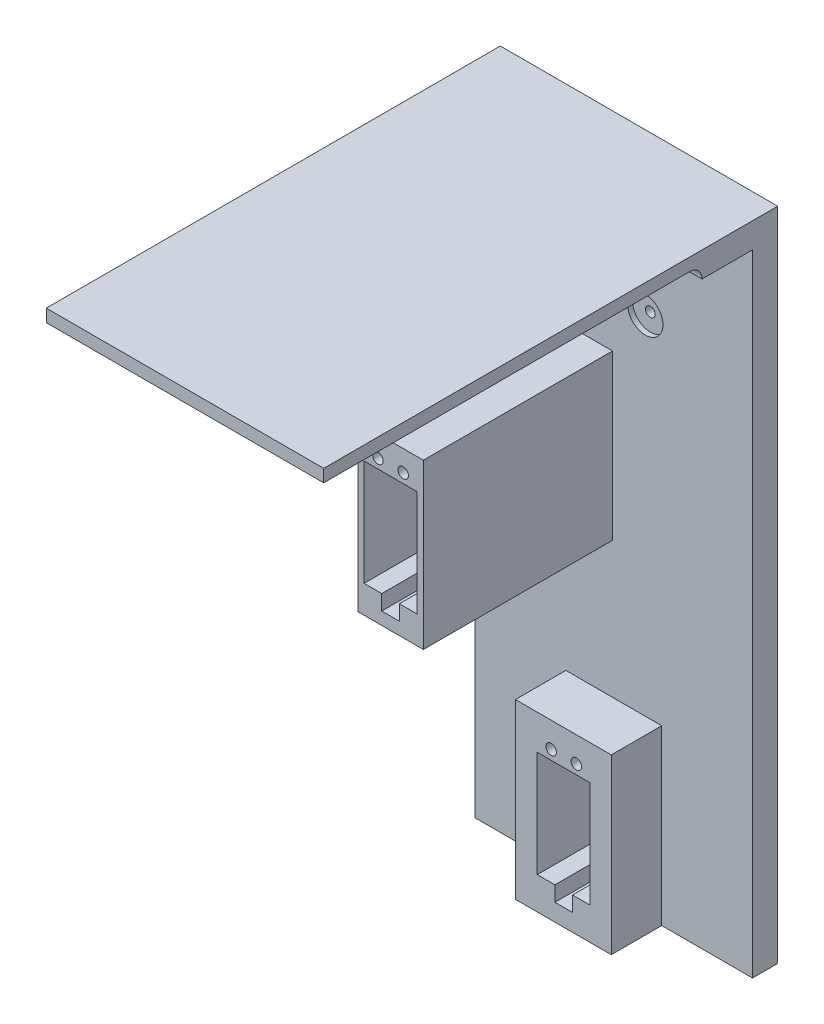
SolidWorks part; units mm, degrees
ref_plane "Front Plane" through (0, 0, 0) normal (0, 0, 1) x (1, 0, 0)
ref_plane "Top Plane" through (0, 0, 0) normal (0, 1, 0) x (1, 0, 0)
ref_plane "Right Plane" through (0, 0, 0) normal (1, 0, 0) x (0, 0, -1)
sketch "Sketch1" plane through (0, 0, 0) normal (0, 0, 1) x (1, 0, 0)
  line L1 (-75, 100) -> (75, 100)
  line L2 (-75, 100) -> (-75, -100)
  line L3 (-75, -100) -> (75, -100)
  line L4 (75, 100) -> (75, -100)
  line L5 (-75, 100) -> (75, -100) construction
  line L6 (-75, -100) -> (75, 100) construction
  point P0 (0, 0)
  dimension "D1" = 200
  dimension "D2" = 150
extrude "Boss-Extrude1" add sketch "Sketch1" along normal blind 30
sketch "Sketch2" plane through (0, 0, 30) normal (0, 0, 1) x (1, 0, 0)
  line L0 (75, -100) -> (75, 100) construction
  line L1 (-75, 100) -> (75, 100)
  line L2 (-75, 100) -> (-75, 95)
  line L3 (-75, 95) -> (75, 95)
  line L4 (75, 100) -> (75, 95)
  dimension "D1" = 5
extrude "Boss-Extrude2" add sketch "Sketch2" along normal blind 150
sketch "Sketch3" plane through (0, 0, 30) normal (0, 0, 1) x (1, 0, 0)
  line L0 (0, -100) -> (0, 0)
  line L1 (-75, -100) -> (75, -100) construction
  line L4 (0, 46.5) -> (0, 71.5)
  line L9 (-10.3251, 73.9819) -> (12.4051, 43.2014) construction
  line L10 (-12.4051, 43.2014) -> (10.3251, 73.9819) construction
  line L11 (-39.5, 13) -> (-39.5, 7)
  line L25 (-43, 13) -> (-36, 7) construction
  line L26 (-43, 7) -> (-36, 13) construction
  line L27 (-15.8, 46.5) -> (-12.5, 46.5)
  line L28 (-12.5, 46.5) -> (12.5, 46.5)
  line L29 (-12.5, 59) -> (12.5, 59)
  line L30 (12.5, 46.5) -> (-12.5, 46.5)
  line L31 (12.5, 46.5) -> (12.5, 71.5)
  line L32 (12.5, 71.5) -> (-12.5, 71.5)
  line L33 (-12.5, 46.5) -> (-12.5, 71.5)
  circle A0 centre (12.5, 46.5) radius 1.65
  circle A1 centre (-12.5, 46.5) radius 1.65
  circle A2 centre (12.5, 71.5) radius 1.65
  circle A3 centre (-12.5, 71.5) radius 1.65
  circle A4 centre (-12.5, 71.5) radius 3.3
  circle A5 centre (12.5, 71.5) radius 3.3
  circle A6 centre (12.5, 46.5) radius 3.3
  circle A7 centre (-12.5, 46.5) radius 3.3
  point P5 (0, 60)
  point P22 (-39.5, 10)
  dimension "D13" = 3.3
  dimension "D14" = 6.6
  dimension "D7" = 6
  dimension "D8" = 7
  dimension "D11" = 25
  dimension "D12" = 25
extrude "Cut-Extrude3" cut sketch "Sketch3" against normal blind 80 contours L11 | L11 | A1 L27 L33 | A1 L28 L27 | A1 L33 L28 | L31 A0 L30 | L30 A0 L31 | A2 L32 L31 | A2 L31 L32 | L32 A3 L33 | L33 A3 L32 region at (-12.5, 45.7997, 30) region at (-11.7997, 47.2003, 30) region at (11.7997, 47.2003, 30) region at (12.7334, 46.2666, 30) region at (-13.2003, 47.2003, 30) region at (-11.7997, 70.7997, 30) region at (-12.7334, 71.7334, 30) region at (12.7334, 71.7334, 30) region at (11.7997, 70.7997, 30)
ref_plane "Plane1" through (0, 0, 30) normal (0, 0, 1) x (1, 0, 0)
sketch "Sketch6" plane through (0, 0, 30) normal (0, 0, 1) x (1, 0, 0)
  circle A0 centre (-12.5, 71.5) radius 5
  circle A1 centre (12.5, 71.5) radius 5
  circle A2 centre (-12.5, 46.5) radius 5
  circle A3 centre (12.5, 46.5) radius 5
  dimension "D1" = 10
  dimension "D2" = 10
  dimension "D3" = 10
  dimension "D4" = 10
extrude "Cut-Extrude5" cut sketch "Sketch6" against normal blind 22
sketch "Sketch7" plane through (0, 0, 8) normal (0, 0, 1) x (1, 0, 0)
  circle A0 centre (-12.5, 71.5) radius 1.925
  circle A1 centre (12.5, 71.5) radius 1.925
  circle A2 centre (-12.5, 46.5) radius 1.925
  circle A3 centre (12.5, 46.5) radius 1.925
  dimension "D1" = 3.85
  dimension "D2" = 3.85
  dimension "D3" = 3.85
  dimension "D4" = 3.85
extrude "Cut-Extrude6" cut sketch "Sketch7" against normal blind 5
sketch "Sketch9" plane through (0, 0, 30) normal (0, 0, 1) x (1, 0, 0)
  line L0 (-12.5, 46.5) -> (12.5, 46.5)
  line L1 (12.5, 46.5) -> (0, 46.5)
  line L2 (0, 46.5) -> (1.1812, -69.9316)
  line L3 (1.1812, -69.9316) -> (1.1812, -115.5276)
  line L4 (-13.5, 15.5) -> (0.3145, 15.5)
  line L5 (-2.604, -89.8179) -> (4.396, -89.8179)
  line L6 (11.396, -83.8179) -> (11.396, -41.8179)
  line L7 (-2.604, -83.8179) -> (-9.604, -83.8179)
  line L8 (4.396, -89.8179) -> (4.396, -83.8179)
  line L9 (4.396, -83.8179) -> (11.396, -83.8179)
  line L10 (-9.604, -41.8179) -> (-9.604, -83.8179)
  line L11 (-24, 15.5) -> (-3, 15.5)
  line L12 (-17, -26.5) -> (-24, -26.5)
  line L18 (-24, 15.5) -> (-24, -26.5)
  line L19 (-10, -32.5) -> (-10, -26.5)
  line L20 (-17, -32.5) -> (-10, -32.5)
  line L21 (-17, -26.5) -> (-17, -32.5)
  line L22 (-10, -26.5) -> (-3, -26.5)
  line L23 (-3, -26.5) -> (-3, 15.5)
  line L24 (-9.604, -41.8179) -> (11.396, -41.8179)
  line L25 (-2.604, -83.8179) -> (-2.604, -89.8179)
  circle A6 centre (-8.5, 19.25) radius 2.08
  circle A7 centre (-18.5, 19.25) radius 2.08
  circle A8 centre (5.896, -38.0679) radius 2.08
  circle A9 centre (-4.104, -38.0679) radius 2.08
  point P16 (-39.5, 65.9329)
  dimension "D6" = 42
  dimension "D1" = 13.8145
fillet "Fillet1" radius 5 1 edges at (0, 95, 30)
extrude "Cut-Extrude7" cut sketch "Sketch9" against normal blind 30 contours L22 L23 L11 L18 L12 L21 L20 L19 | A7 | A6 region at (-13.5, -6.5909, 30) region at (-8.5, 19.25, 30) region at (-18.5, 19.25, 30)
sketch "Sketch10" plane through (0, 0, 30) normal (0, 0, 1) x (1, 0, 0)
  line L8 (0.1568, -105.1715) -> (0.1568, -105.1715)
  line L9 (8.2068, -105.9215) -> (-7.8932, -105.9215) construction
ref_plane "Plane2" through (0, 0, 0) normal (0, 0, -1) x (-1, 0, 0)
sketch "Sketch12" plane through (0, 0, 0) normal (0, 0, -1) x (-1, 0, 0)
  line L0 (13.5, 15.5) -> (13.5, -37.4614)
  line L1 (24, 15.5) -> (3, 15.5) construction
  line L2 (13.5, -37.4614) -> (26.5, -37.4614)
  line L3 (26.5, -37.4614) -> (26.5, 27.5386)
  line L4 (3, 15.5) -> (3, -26.5)
  line L5 (26.5, -37.4614) -> (0.5, -37.4614)
  line L6 (26.5, -37.4614) -> (26.5, 27.5386)
  line L7 (26.5, 27.5386) -> (0.5, 27.5386)
  line L8 (0.5, -37.4614) -> (0.5, 27.5386)
  line L9 (3, -26.5) -> (10, -26.5)
  line L10 (10, -26.5) -> (10, -32.5)
  line L11 (10, -32.5) -> (17, -32.5)
  line L12 (17, -32.5) -> (17, -26.5)
  line L13 (17, -26.5) -> (24, -26.5)
  line L14 (24, -26.5) -> (24, 15.5)
  line L15 (24, 15.5) -> (3, 15.5)
  circle A0 centre (8.5, 19.25) radius 2.08
  circle A1 centre (18.5, 19.25) radius 2.08
  dimension "D1" = 13
  dimension "D2" = 65
  dimension "D3" = 26
  dimension "D4" = 65
extrude "Boss-Extrude5" add sketch "Sketch12" against normal blind 85 contours L15 L14 L13 L12 L11 L2 L3 L7 L8 L5 L10 L9 L4 A1 A0 region at (-7, -36.7613, 0)
sketch "Sketch13" plane through (0, 0, 0) normal (0, 0, -1) x (-1, 0, 0)
  line L0 (-75, -100) -> (-75, -160)
  line L1 (-75, -160) -> (75, -160)
  line L2 (75, -160) -> (75, -100)
  line L3 (75, -100) -> (-75, -100) construction
  line L4 (75, -100) -> (-75, -100)
  dimension "D1" = 60
extrude "Boss-Extrude6" add sketch "Sketch13" against normal blind 30
sketch "Sketch15" plane through (0, 0, 30) normal (0, 0, 1) x (1, 0, 0)
  line L0 (-10.3432, -105.1715) -> (10.6568, -105.1715)
  line L1 (10.6568, -105.1715) -> (10.6568, -147.1715)
  line L2 (10.6568, -147.1715) -> (3.6568, -147.1715)
  line L3 (3.6568, -147.1715) -> (3.6568, -153.1715)
  line L4 (3.6568, -153.1715) -> (-3.3432, -153.1715)
  line L5 (-3.3432, -153.1715) -> (-3.3432, -147.1715)
  line L6 (-3.3432, -147.1715) -> (-10.3432, -147.1715)
  line L7 (-10.3432, -147.1715) -> (-10.3432, -105.1715)
  circle A0 centre (-4.8432, -101.4215) radius 2.08
  circle A1 centre (5.1568, -101.4215) radius 2.08
  dimension "D1" = 4.16
  dimension "D2" = 4.16
extrude "Cut-Extrude8" cut sketch "Sketch15" against normal blind 30
sketch "Sketch16" plane through (0, 0, 30) normal (0, 0, 1) x (1, 0, 0)
  circle A0 centre (-12.5, 71.5) radius 7
  circle A1 centre (12.5, 71.5) radius 7
  circle A2 centre (12.5, 46.5) radius 7
  circle A3 centre (-12.5, 46.5) radius 7
  dimension "D1" = 14
extrude "Cut-Extrude9" cut sketch "Sketch16" against normal blind 22
sketch "Sketch17" plane through (0, 0, 0) normal (0, 0, -1) x (-1, 0, 0)
  line L0 (-75, -160) -> (75, -160) construction
  line L1 (75, 100) -> (55, 100)
  line L2 (75, 100) -> (75, -160)
  line L3 (75, -160) -> (55, -160)
  line L4 (55, 100) -> (55, -160)
  line L5 (-55, -160) -> (-75, -160)
  line L6 (-75, 100) -> (-75, -160)
  line L7 (-55, 100) -> (-75, 100)
  line L8 (-55, 100) -> (-55, -160)
  dimension "D1" = 20
extrude "Cut-Extrude10" cut sketch "Sketch17" against normal blind 180
sketch "Sketch19" plane through (0, 0, 30) normal (0, 0, 1) x (1, 0, 0)
  line L0 (-55, 90) -> (55, 90)
  line L1 (55, 90) -> (55, -160)
  line L2 (55, -160) -> (19, -160)
  line L3 (55, -160) -> (-55, -160) construction
  line L4 (19, -160) -> (19, -91.3882)
  line L5 (19, -91.3882) -> (-19, -91.3882)
  line L6 (-19, -91.3882) -> (-19, -160)
  line L7 (-19, -160) -> (-55, -160)
  line L8 (-55, -160) -> (-55, 90)
  line L9 (-26.5, 27.5386) -> (-26.5, -37.4614)
  line L10 (-26.5, -37.4614) -> (-0.5, -37.4614) construction
  line L11 (-26.5, 27.5386) -> (-26.5, -37.4614) construction
  line L12 (-26.5, -37.4614) -> (-0.5, -37.4614)
  line L13 (-0.5, -37.4614) -> (-0.5, 27.5386)
  line L14 (-0.5, 27.5386) -> (-26.5, 27.5386)
  dimension "D1" = 36
  dimension "D2" = 36
extrude "Cut-Extrude11" cut sketch "Sketch19" against normal blind 20
